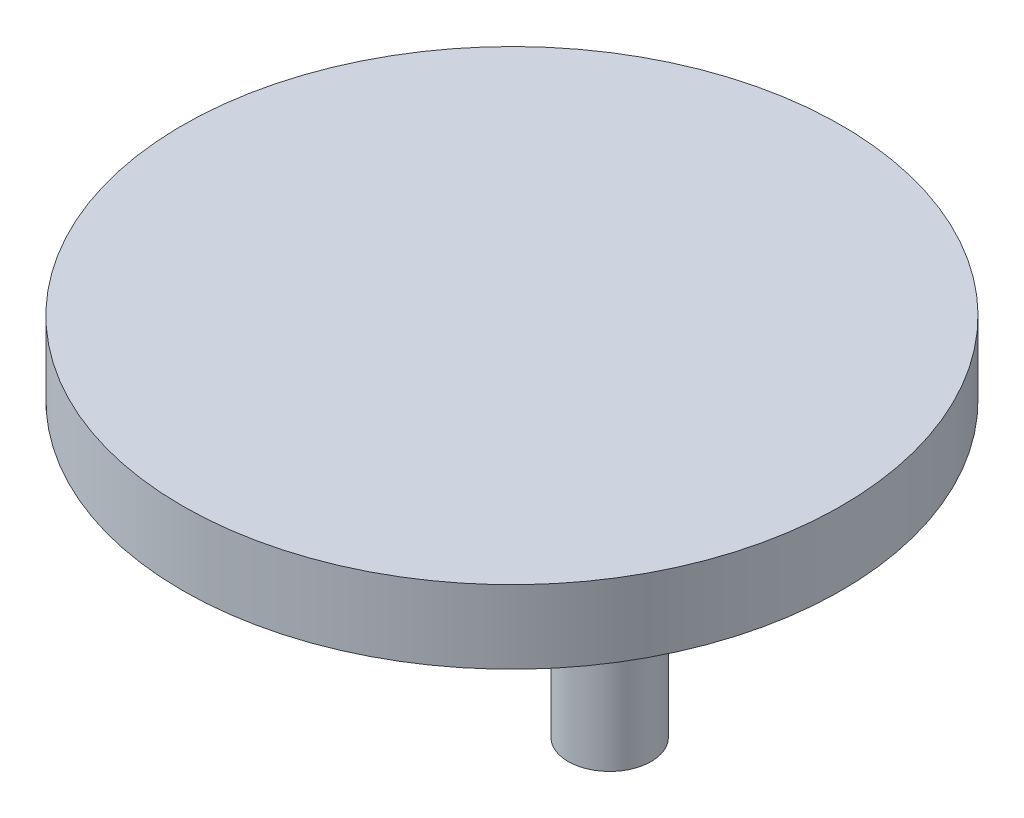
SolidWorks part; units mm, degrees
ref_plane "Front Plane" through (0, 0, 0) normal (0, 0, 1) x (1, 0, 0)
ref_plane "Top Plane" through (0, 0, 0) normal (0, 1, 0) x (1, 0, 0)
ref_plane "Right Plane" through (0, 0, 0) normal (1, 0, 0) x (0, 0, -1)
sketch "Sketch1" plane through (0, 0, 0) normal (0, 1, 0) x (1, 0, 0)
  line L0 (0, 0) -> (0, 21.875) construction
  circle A0 centre (0, 21.875) radius 3.4
  circle A1 centre (18.9443, -10.9375) radius 3.4
  circle A2 centre (-18.9443, -10.9375) radius 3.4
  point P11 (0, 0)
  dimension "D1" = 6.8
  dimension "D2" = 3
sketch "Sketch2" plane through (0, 0, 0) normal (0, 1, 0) x (1, 0, 0)
  circle A0 centre (0, 0) radius 27
  dimension "D1" = 54
extrude "Boss-Extrude1" add sketch "Sketch2" along normal blind 6
extrude "Boss-Extrude2" add sketch "Sketch1" against normal blind 9 contours A1 | A0 | A2 region at (0, 0, -21.875) region at (18.9443, 0, 10.9375)
